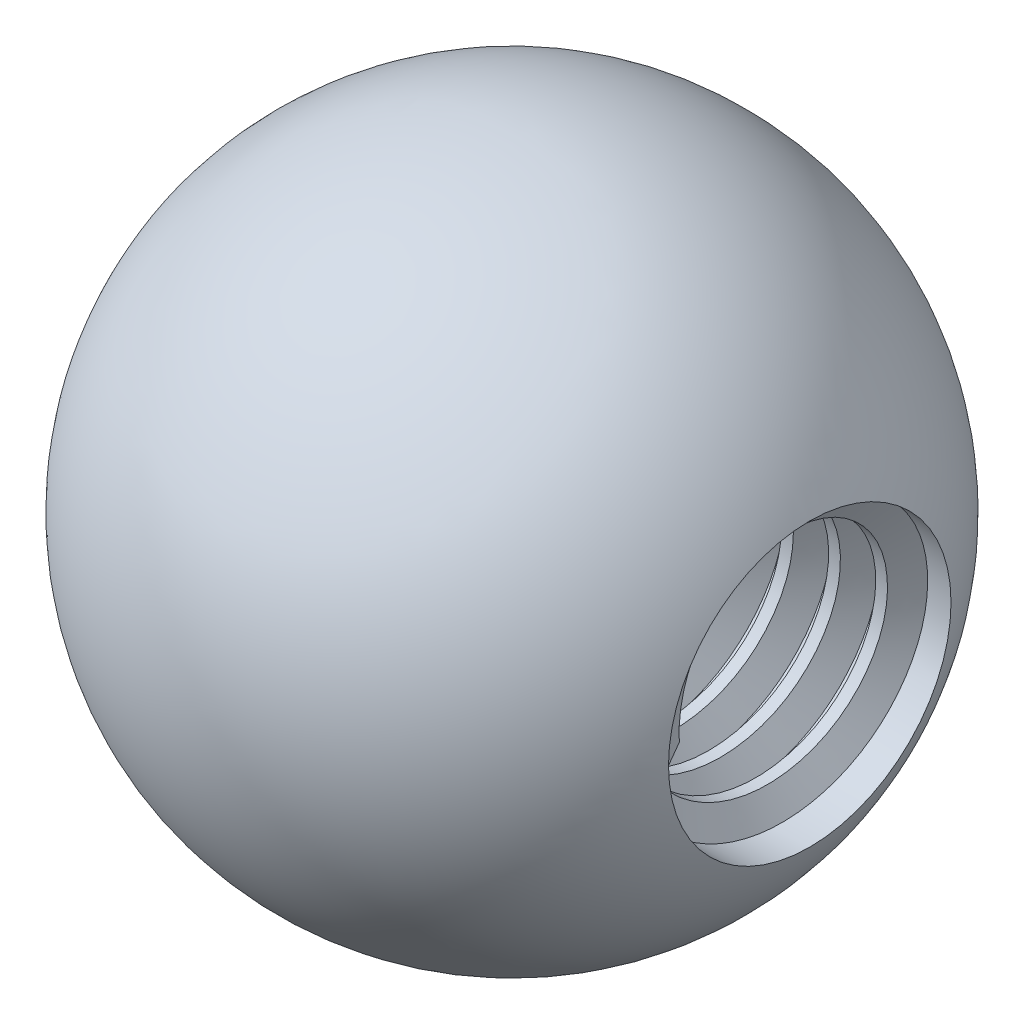
SolidWorks part; units mm, degrees
ref_plane "Front Plane" through (0, 0, 0) normal (0, 0, 1) x (1, 0, 0)
ref_plane "Top Plane" through (0, 0, 0) normal (0, 1, 0) x (1, 0, 0)
ref_plane "Right Plane" through (0, 0, 0) normal (1, 0, 0) x (0, 0, -1)
sketch "Sketch1" plane through (0, 0, 0) normal (0, 0, 1) x (1, 0, 0)
  line L0 (0, 0) -> (-13.9714, 0) construction
  line L1 (0, 0) -> (11.0873, 0) construction
  line L2 (-7, 0) -> (7, 0)
  arc A0 (7, 0) -> (-7, 0) centre (0, 0) ccw
  dimension "D1" = 14
revolve "Revolve1" add sketch "Sketch1" angle 360 about L1
ref_plane "Plane1" through (7, 0, 0) normal (1, 0, 0) x (0, 0, -1)
sketch "Sketch8" plane through (7, 0, 0) normal (1, 0, 0) x (0, 0, -1)
  circle A0 centre (0, 0) radius 3
  dimension "D1" = 6
extrude "Cut-Extrude1" cut sketch "Sketch8" against normal blind 7
thread "Thread1" pitch 1 method extrude profile "Thread Profile1" start angle 0, offset 0, length 7, pitch 1, diameter 6
ref_plane "Plane2" through (6.3246, 0, 3) normal (0, -1, 0) x (0, 0, 1)
sketch "Thread Profile1" plane through (6.3246, 0, 3) normal (0, -1, 0) x (0, 0, 1)
  line L0 (0, 0) -> (0, 1) construction
  line L11 (0, 0) -> (0, 0.875)
  line L12 (0, 0.875) -> (-0.5413, 0.5625)
  line L13 (-0.5413, 0.5625) -> (-0.5413, 0.3125)
  line L15 (-0.5413, 0.3125) -> (0, 0)
  line L17 (-0.5413, 0.4375) -> (0, 0.4375) construction
  point P2 (0, 0)
  dimension "Pitch" = 1
  dimension "Profile_Angle" = 60
  dimension "Profile_Land" = 0.25
  dimension "Profile_Height" = 0.5413
